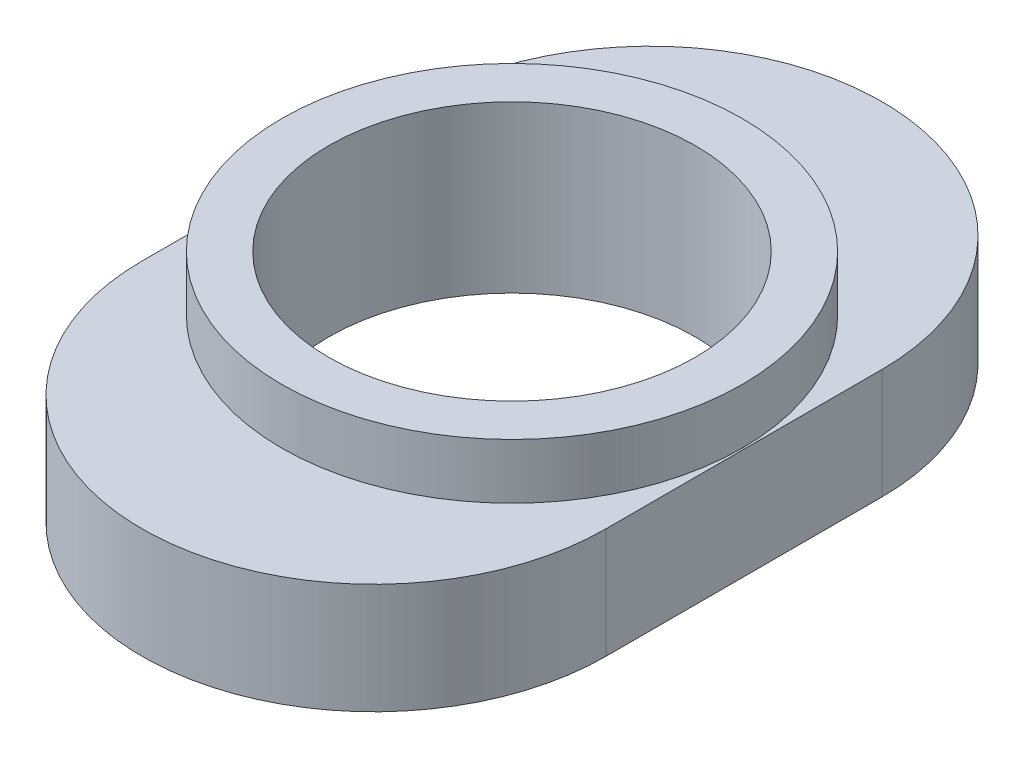
SolidWorks part; units mm, degrees
ref_plane "Front Plane" through (0, 0, 0) normal (0, 0, 1) x (1, 0, 0)
ref_plane "Top Plane" through (0, 0, 0) normal (0, 1, 0) x (1, 0, 0)
ref_plane "Right Plane" through (0, 0, 0) normal (1, 0, 0) x (0, 0, -1)
sketch "Sketch1" plane through (0, 0, 0) normal (0, 1, 0) x (1, 0, 0)
  line L0 (0, 3.175) -> (0, -3.175) construction
  line L1 (5.334, 3.175) -> (5.334, -3.175)
  line L2 (-5.334, 3.175) -> (-5.334, -3.175)
  arc A0 (5.334, 3.175) -> (-5.334, 3.175) centre (0, 3.175) ccw
  arc A1 (-5.334, -3.175) -> (5.334, -3.175) centre (0, -3.175) ccw
  point P2 (0, 0)
  dimension "D2" = 3.175
  dimension "D1" = 10.668
extrude "Boss-Extrude1" add sketch "Sketch1" along normal blind 2.54 contours A0 L2 A1 L1
sketch "Sketch2" plane through (0, 2.54, 0) normal (0, 1, 0) x (1, 0, 0)
  circle A0 centre (0, 0) radius 4.2164
  dimension "D1" = 8.4328
extrude "Cut-Extrude1" cut sketch "Sketch2" against normal blind 2.54 contours A0
sketch "Sketch3" plane through (0, 2.54, 0) normal (0, 1, 0) x (1, 0, 0)
  circle A0 centre (0, 0) radius 4.2164
extrude "Extrude-Thin1" add sketch "Sketch3" along normal blind 1.27 thin thin type one direction wall 1.0795
